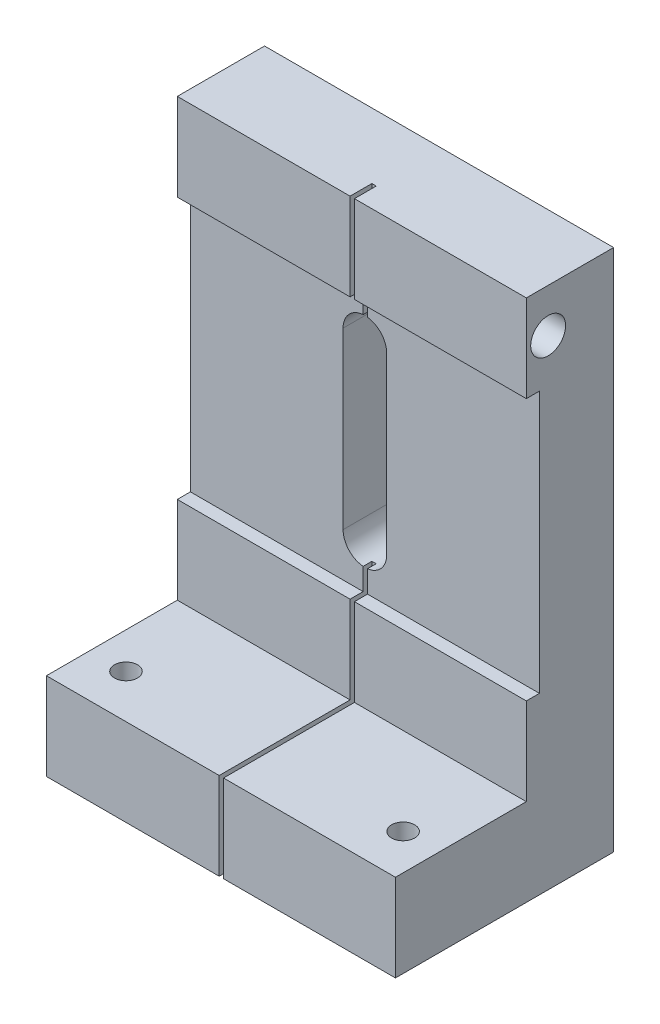
SolidWorks part; units mm, degrees
ref_plane "Front Plane" through (0, 0, 0) normal (0, 0, 1) x (1, 0, 0)
ref_plane "Top Plane" through (0, 0, 0) normal (0, 1, 0) x (1, 0, 0)
ref_plane "Right Plane" through (0, 0, 0) normal (1, 0, 0) x (0, 0, -1)
sketch "Sketch1" plane through (0, 0, 0) normal (0, 0, 1) x (1, 0, 0)
  line L1 (0, 0) -> (-40, 0)
  line L2 (0, 0) -> (0, -60)
  line L3 (0, -60) -> (-40, -60)
  line L4 (-40, 0) -> (-40, -60)
  dimension "D1" = 40
  dimension "D2" = 60
extrude "Boss-Extrude1" add sketch "Sketch1" along normal blind 10
sketch "Sketch2" plane through (0, 0, 10) normal (0, 0, 1) x (1, 0, 0)
  line L0 (-20, -15) -> (-20, -35) construction
  line L1 (-17.5, -15) -> (-17.5, -35)
  line L2 (-22.5, -15) -> (-22.5, -35)
  line L3 (0, -60) -> (0, 0) construction
  line L4 (-40, -60) -> (0, -60) construction
  arc A0 (-17.5, -15) -> (-22.5, -15) centre (-20, -15) ccw
  arc A1 (-22.5, -35) -> (-17.5, -35) centre (-20, -35) ccw
  point P2 (-20, -25)
  dimension "D1" = 5
  dimension "D2" = 20
  dimension "D3" = 20
  dimension "D4" = 35
extrude "Cut-Extrude1" cut sketch "Sketch2" against normal through all
sketch "Sketch5" plane through (0, 0, 0) normal (1, 0, 0) x (0, 0, -1)
  line L0 (-8.5, -10) -> (-10, -10)
  line L1 (-10, -60) -> (-10, 0) construction
  line L2 (-8.5, -10) -> (-8.5, -40)
  line L3 (-10, -60) -> (0, -60) construction
  line L4 (-8.5, -40) -> (-10, -40)
  line L7 (-10, -10) -> (-10, -40)
  dimension "D1" = 1.5
  dimension "D4" = 30
  dimension "D5" = 20
extrude "Cut-Extrude4" cut sketch "Sketch5" against normal through all
sketch "Sketch6" plane through (0, 0, 10) normal (0, 0, 1) x (1, 0, 0)
  line L0 (-40, -40) -> (-40, -60) construction
  line L1 (0, -60) -> (-40, -60)
  line L2 (0, -60) -> (0, -50)
  line L3 (0, -50) -> (-40, -50)
  line L4 (-40, -60) -> (-40, -50)
  dimension "D1" = 10
extrude "Boss-Extrude2" add sketch "Sketch6" along normal blind 15
sketch "Sketch7" plane through (0, -50, 0) normal (0, 1, 0) x (1, 0, 0)
  line L3 (-40, -25) -> (-40, -10) construction
  circle A0 centre (-4.125, -15.1829) radius 2
  circle A1 centre (-35.875, -15.1829) radius 2
  dimension "D1" = 4
  dimension "D2" = 4
  dimension "D3" = 4.125
  dimension "D5" = 31.75
extrude "Cut-Extrude5" [suppressed] cut sketch "Sketch7" against normal blind 40
sketch "Sketch8" plane through (0, 0, 0) normal (0, 1, 0) x (1, 0, 0)
  line L2 (-20.2, -25) -> (-19.7, -25)
  line L5 (-20.2, -25) -> (-20.2, -7.5)
  line L7 (0, -25) -> (-40, -25) construction
  line L9 (-20.2, -7.5) -> (-19.7, -7.5)
  line L10 (-19.7, -25) -> (-19.7, -7.5)
  line L11 (-22.5, 0) -> (-22.5, -8.5) construction
  dimension "D1" = 0.5
  dimension "D2" = 2.3
  dimension "D3" = 17.5
extrude "Cut-Extrude7" cut sketch "Sketch8" against normal up to surface (60 mm away) up to face at (-20, -60, 12.5)
sketch "Sketch9" plane through (0, -60, 0) normal (0, -1, 0) x (1, 0, 0)
  line L3 (0, 25) -> (0, 0) construction
  line L5 (-40, 8.5) -> (-20.2, 8.5) construction
  circle A0 centre (-32.7, 6.5) radius 2
  circle A1 centre (-7.3, 6.5) radius 2
  dimension "D1" = 4
  dimension "D3" = 7.3
  dimension "D4" = 4
  dimension "D2" = 25.4
extrude "Cut-Extrude9" [suppressed] cut sketch "Sketch9" against normal blind 15
sketch "Sketch10" plane through (0, 0, 0) normal (1, 0, 0) x (0, 0, -1)
  line L1 (-10, 0) -> (0, 0) construction
  line L2 (-10, -10) -> (-10, 0) construction
  circle A0 centre (-7.5, -5) radius 2
  dimension "D1" = 4
  dimension "D2" = 5
  dimension "D3" = 2.5
extrude "Cut-Extrude10" cut sketch "Sketch10" against normal blind 30
sketch "Sketch12" plane through (0, -60, 0) normal (0, -1, 0) x (1, 0, 0)
  line L0 (-40, 0) -> (0, 0) construction
  line L1 (-40, 25) -> (-40, 0) construction
  circle A0 centre (-35.87, 4.13) radius 1.32
  circle A1 centre (-19.99, 4.13) radius 1.32
  circle A2 centre (-4.11, 4.13) radius 1.32
  circle A4 centre (-4.11, 20.01) radius 1.32
  circle A5 centre (-35.87, 20.01) radius 1.32
  circle A6 centre (-19.99, 20.01) radius 1.32 [skipped]
  dimension "D1" = 2.64
  dimension "D2" = 4.13
  dimension "D3" = 4.13
  dimension "D4" = 3
  dimension "D5" = 2
extrude "Cut-Extrude11" cut sketch "Sketch12" against normal up to surface (10 mm away) up to face at (-9.85, -50, 17.5)
equation "\"inch\"=25.4"
equation "\"D5@Sketch7\"=\"inch\"*1.25"
equation "\"D2@Sketch9\"=\"inch\""
